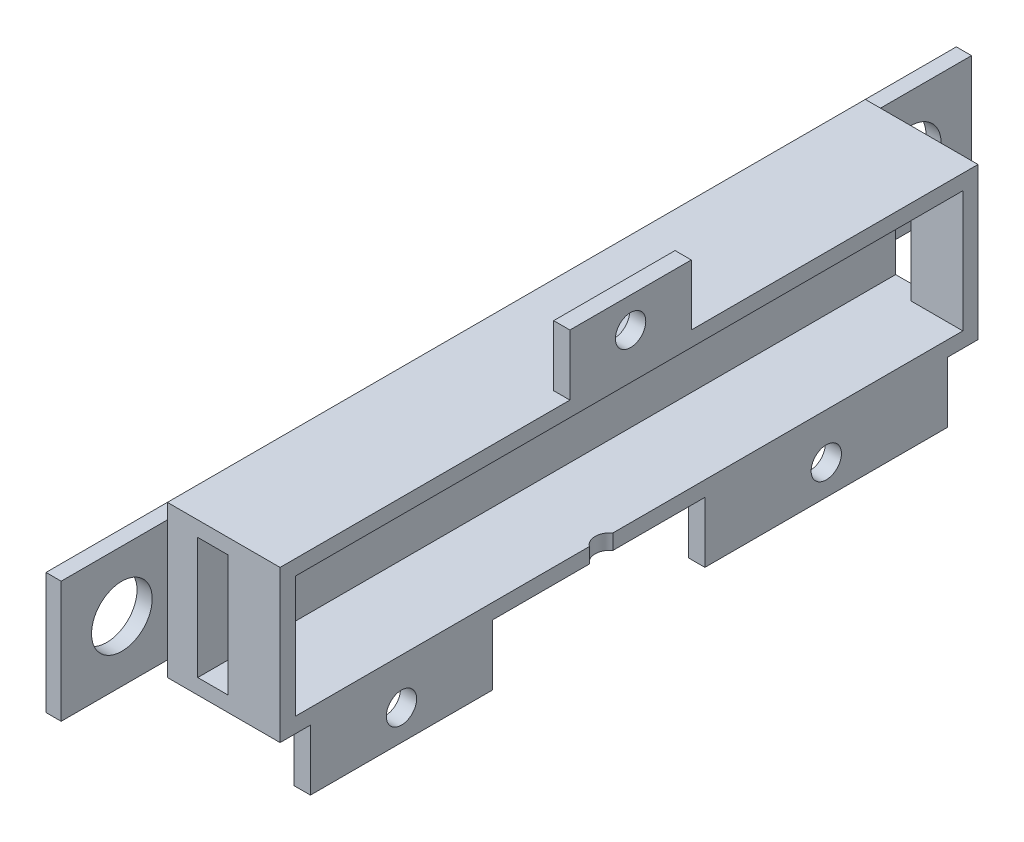
SolidWorks part; units mm, degrees
ref_plane "Front" through (0, 0, 0) normal (0, 0, 1) x (1, 0, 0)
ref_plane "Top" through (0, 0, 0) normal (0, 1, 0) x (1, 0, 0)
ref_plane "Right" through (0, 0, 0) normal (1, 0, 0) x (0, 0, -1)
sketch "Sketch1" plane through (0, 0, 0) normal (1, 0, 0) x (0, 0, -1)
  line L0 (-145.5208, 2.1167) -> (-145.5208, 14.8167)
  line L1 (-132.8208, 14.8167) -> (32.2792, 14.8167)
  line L2 (-132.8208, 14.8167) -> (-132.8208, -10.5833)
  line L3 (-132.8208, -10.5833) -> (32.2792, -10.5833)
  line L4 (32.2792, 14.8167) -> (32.2792, -10.5833)
  line L5 (-145.5208, 14.8167) -> (-132.8208, 14.8167)
  line L6 (-145.5208, 2.1167) -> (-145.5208, -10.5833)
  line L7 (-145.5208, -10.5833) -> (-132.8208, -10.5833)
  line L8 (44.9792, 2.1167) -> (44.9792, -10.5833)
  line L9 (44.9792, -10.5833) -> (32.2792, -10.5833)
  line L10 (32.2792, 14.8167) -> (44.9792, 14.8167)
  line L11 (44.9792, 14.8167) -> (44.9792, 2.1167)
  line L13 (-145.5208, 14.8167) -> (44.9792, 14.8167)
  line L14 (-145.5208, 14.8167) -> (-145.5208, -10.5833)
  line L15 (-145.5208, -10.5833) -> (44.9792, -10.5833)
  line L16 (44.9792, 14.8167) -> (44.9792, -10.5833)
  circle A2 centre (-132.8208, 2.1167) radius 6.35
  circle A3 centre (32.2792, 2.1167) radius 6.35
  dimension "D3" = 12.7
  dimension "D4" = 165.1
  dimension "D2" = 25.4
extrude "Boss-Extrude1" add sketch "Sketch1" along normal blind 3.175 contours A2 L2 L5 L0 L6 L7 | A3 L4 L1 L2 A2 L3 | A3 L4 L9 L8 L11 L10 region at (0, 2.1167, 140.0638) region at (0, 2.1167, 50.2708) region at (0, 2.1167, -39.5222)
sketch "Sketch2" plane through (3.175, 0, 0) normal (1, 0, 0) x (0, 0, -1)
  line L0 (-145.5208, -10.5833) -> (44.9792, -10.5833) construction
  line L1 (-145.5208, 14.8167) -> (45.002, 14.8167)
  line L2 (-145.5208, 14.8167) -> (-145.5208, 17.9917)
  line L3 (-145.5208, 17.9917) -> (45.002, 17.9917)
  line L4 (45.002, 14.8167) -> (45.002, 17.9917)
  line L5 (-123.2958, 14.8167) -> (22.7542, 14.8167)
  line L6 (-123.2958, 14.8167) -> (-123.2958, -10.5833)
  line L7 (-123.2958, -10.5833) -> (22.7542, -10.5833)
  line L8 (22.7542, 14.8167) -> (22.7542, -10.5833)
  line L9 (44.9792, 14.8167) -> (44.9792, -10.5833) construction
  line L10 (-145.5208, -10.5833) -> (45.002, -10.5833)
  line L11 (-145.5208, -10.5833) -> (-145.5208, -13.7583)
  line L12 (-145.5208, -13.7583) -> (45.002, -13.7583)
  line L13 (45.002, -10.5833) -> (45.002, -13.7583)
  line L14 (-145.5208, -10.5833) -> (-145.5208, 14.8167) construction
  line L15 (-123.2958, -10.5833) -> (-123.2958, -13.7583)
  line L16 (-123.2958, 14.8167) -> (-123.2958, 17.9917)
  line L17 (22.7542, -10.5833) -> (22.7542, -13.7583)
  line L18 (22.7542, 14.8167) -> (22.7542, 17.9917)
  line M12 (-145.5208, -10.5833) -> (44.9792, -10.5833)
  dimension "D1" = 3.175
  dimension "D2" = 3.175
  dimension "D3" = 22.225
  dimension "D4" = 22.225
extrude "Boss-Extrude2" add sketch "Sketch2" along normal blind 47.625 separate body contours L17 L15 L12 M12 | L1 L18 L3 L16 region at (3.175, 16.4042, 50.2708) region at (3.175, -12.1708, 50.2708)
sketch "Sketch3" plane through (3.175, 0, 0) normal (1, 0, 0) x (0, 0, -1)
  line L1 (-123.2958, 14.8167) -> (22.7542, 14.8167)
  line L2 (-123.2958, 14.8167) -> (-123.2958, -10.5833)
  line L3 (-123.2958, -10.5833) -> (22.7542, -10.5833)
  line L4 (22.7542, 14.8167) -> (22.7542, -10.5833)
extrude "Boss-Extrude4" add sketch "Sketch3" along normal blind 6.35
sketch "Sketch4" plane through (9.525, 0, 0) normal (1, 0, 0) x (0, 0, -1)
  line L6 (-123.2958, -10.5833) -> (22.7542, -10.5833) construction
  line L7 (-123.2958, 14.8167) -> (-120.1208, 14.8167)
  line L8 (-123.2958, 14.8167) -> (-123.2958, -10.5833)
  line L9 (-123.2958, -10.5833) -> (-120.1208, -10.5833)
  line L10 (-120.1208, 14.8167) -> (-120.1208, -10.5833)
  line L12 (22.7542, 14.8167) -> (19.5792, 14.8167)
  line L13 (22.7542, 14.8167) -> (22.7542, -10.5833)
  line L14 (22.7542, -10.5833) -> (19.5792, -10.5833)
  line L15 (19.5792, 14.8167) -> (19.5792, -10.5833)
  dimension "D1" = 3.175
  dimension "D2" = 3.175
extrude "Boss-Extrude5" add sketch "Sketch4" along normal blind 41.275
sketch "Sketch5" plane through (0, 0, 123.2958) normal (0, 0, 1) x (1, 0, 0)
  line L0 (50.8, 17.9917) -> (3.175, 17.9917) construction
  line L1 (9.525, 17.9917) -> (15.875, 17.9917)
  line L2 (9.525, 17.9917) -> (9.525, -13.7583)
  line L3 (9.525, -13.7583) -> (15.875, -13.7583)
  line L4 (15.875, 17.9917) -> (15.875, -13.7583)
  line L5 (50.8, -13.7583) -> (3.175, -13.7583) construction
  line L6 (3.175, 14.8167) -> (3.175, -10.5833) construction
  line L7 (9.525, 14.8167) -> (15.875, 14.8167)
  line L8 (9.525, -10.5833) -> (15.875, -10.5833)
  dimension "D1" = 6.35
  dimension "D2" = 6.35
  dimension "D3" = 3.175
  dimension "D4" = 3.175
extrude "Cut-Extrude1" cut sketch "Sketch5" against normal blind 165.45 contours L2 L8 L4 L7 region at (12.7, 2.1167, 123.2958)
sketch "Sketch7" plane through (50.8, 0, 0) normal (1, 0, 0) x (0, 0, -1)
  line L1 (-123.2958, 17.9917) -> (22.7542, 17.9917)
  line L2 (-123.2958, 17.9917) -> (-123.2958, -13.7583)
  line L3 (-123.2958, -13.7583) -> (22.7542, -13.7583)
  line L4 (22.7542, 17.9917) -> (22.7542, -13.7583)
extrude "Boss-Extrude7" add sketch "Sketch7" along normal blind 3.175
fillet "Fillet1" radius 10 4 edges at (53.975, 17.9917, 50.2708) (53.975, 2.1167, -22.7542) (53.975, -13.7583, 50.2708) (53.975, 2.1167, 123.2958)
sketch "Sketch8" plane through (0, -13.7583, 0) normal (0, -1, 0) x (1, 0, 0)
  line L0 (43.975, 123.2958) -> (3.175, 123.2958) construction
  line L3 (3.175, 123.2958) -> (3.175, -22.7542) construction
  circle A0 centre (28.575, 56.1208) radius 3.05
  dimension "D3" = 6.1
  dimension "D1" = 67.175
  dimension "D2" = 25.4
extrude "Cut-Extrude2" cut sketch "Sketch8" against normal blind 3.175
sketch "Sketch9" plane through (0, -13.7583, 0) normal (0, -1, 0) x (1, 0, 0)
  line L0 (43.975, 123.2958) -> (3.175, 123.2958) construction
  line L1 (29.7167, 116.9458) -> (23.3667, 116.9458)
  line L2 (29.7167, 116.9458) -> (29.7167, 78.8458)
  line L3 (29.7167, 78.8458) -> (23.3667, 78.8458)
  line L4 (23.3667, 116.9458) -> (23.3667, 78.8458)
  line L5 (29.7167, 34.3958) -> (23.3667, 34.3958)
  line L6 (29.7167, 34.3958) -> (29.7167, -16.4042)
  line L7 (29.7167, -16.4042) -> (23.3667, -16.4042)
  line L8 (23.3667, 34.3958) -> (23.3667, -16.4042)
  line L9 (43.975, -22.7542) -> (3.175, -22.7542) construction
  dimension "D1" = 6.35
  dimension "D2" = 50.8
  dimension "D3" = 6.35
  dimension "D4" = 38.1
  dimension "D5" = 6.35
  dimension "D6" = 6.35
  dimension "D7" = 20.1917
extrude "Boss-Extrude8" add sketch "Sketch9" along normal blind 12.7
sketch "Sketch10" plane through (29.7167, 0, 0) normal (1, 0, 0) x (0, 0, -1)
  line L0 (-34.3958, -26.4583) -> (-34.3958, -13.7583) construction
  line L1 (16.4042, -26.4583) -> (-34.3958, -26.4583) construction
  line L2 (-78.8458, -26.4583) -> (-116.9458, -26.4583) construction
  line L3 (-78.8458, -26.4583) -> (-78.8458, -13.7583) construction
  circle A0 centre (-97.8958, -20.1083) radius 3.175
  circle A1 centre (-8.9958, -20.1083) radius 3.175
  dimension "D1" = 6.35
  dimension "D2" = 6.35
  dimension "D3" = 25.4
  dimension "D4" = 6.35
  dimension "D5" = 6.35
  dimension "D6" = 19.05
extrude "Cut-Extrude3" cut sketch "Sketch10" against normal blind 12.7
sketch "Sketch11" plane through (0, 17.9917, 0) normal (0, 1, 0) x (1, 0, 0)
  line L0 (43.975, 22.7542) -> (3.175, 22.7542) construction
  line L1 (29.715, -37.2458) -> (23.365, -37.2458)
  line L2 (29.715, -37.2458) -> (29.715, -62.6458)
  line L3 (29.715, -62.6458) -> (23.365, -62.6458)
  line L4 (23.365, -37.2458) -> (23.365, -62.6458)
  dimension "D1" = 60
  dimension "D2" = 25.4
  dimension "D3" = 6.35
  dimension "D4" = 20.19
extrude "Boss-Extrude9" add sketch "Sketch11" along normal blind 12.7
sketch "Sketch12" plane through (29.715, 0, 0) normal (1, 0, 0) x (0, 0, -1)
  line L0 (-37.2458, 30.6917) -> (-37.2458, 17.9917) construction
  line L3 (-62.6458, 30.6917) -> (-37.2458, 30.6917) construction
  circle A0 centre (-49.9458, 24.3417) radius 3.175
  dimension "D3" = 6.35
  dimension "D1" = 12.7
  dimension "D2" = 6.35
extrude "Cut-Extrude4" cut sketch "Sketch12" against normal blind 12.7
sketch "Sketch13" plane through (0, -13.7583, 0) normal (0, -1, 0) x (1, 0, 0)
  line L0 (43.975, 123.2958) -> (3.175, 123.2958) construction
  line L1 (26.7612, 123.2958) -> (55.5015, 123.2958)
  line L2 (26.7612, 123.2958) -> (26.7612, -22.8245)
  line L3 (26.7612, -22.8245) -> (55.5015, -22.8245)
  line L4 (55.5015, 123.2958) -> (55.5015, -22.8245)
extrude "Cut-Extrude5" cut sketch "Sketch13" against normal blind 50.8 and the other way blind 50.8
